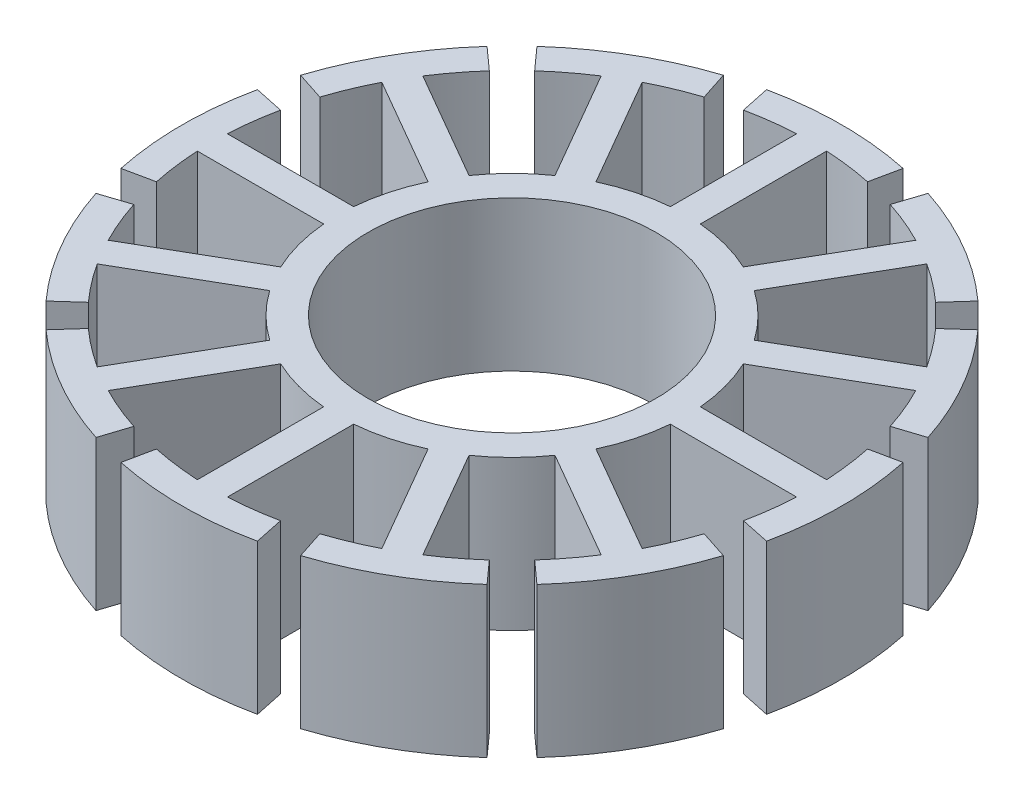
SolidWorks part; units mm, degrees
ref_plane "Front Plane" through (0, 0, 0) normal (0, 0, 1) x (1, 0, 0)
ref_plane "Top Plane" through (0, 0, 0) normal (0, 1, 0) x (1, 0, 0)
ref_plane "Right Plane" through (0, 0, 0) normal (1, 0, 0) x (0, 0, -1)
sketch "Sketch1" plane through (0, 0, 0) normal (0, 1, 0) x (1, 0, 0)
  line L0 (0, 11) -> (0, -11) construction
  line L1 (-0.5, 9.9875) -> (-0.5, 5.7784)
  line L2 (0.5, 9.9875) -> (0.5, 5.7784)
  line L3 (-2.0682, 9.7838) -> (-2.275, 10.7622)
  line L4 (2.0682, 9.7838) -> (2.275, 10.7622)
  line L5 (3.1008, 9.5071) -> (3.4109, 10.4578)
  line L6 (4.5607, 8.8994) -> (2.4562, 5.2542)
  line L7 (5.4268, 8.3994) -> (3.3222, 4.7542)
  line L8 (6.683, 7.4389) -> (7.3513, 8.1828)
  line L9 (7.4389, 6.683) -> (8.1828, 7.3513)
  line L10 (8.3994, 5.4268) -> (4.7542, 3.3222)
  line L11 (8.8994, 4.5607) -> (5.2542, 2.4562)
  line L12 (9.5071, 3.1008) -> (10.4578, 3.4109)
  line L13 (9.7838, 2.0682) -> (10.7622, 2.275)
  line L14 (9.9875, 0.5) -> (5.7784, 0.5)
  line L15 (9.9875, -0.5) -> (5.7784, -0.5)
  line L16 (9.7838, -2.0682) -> (10.7622, -2.275)
  line L17 (9.5071, -3.1008) -> (10.4578, -3.4109)
  line L18 (8.8994, -4.5607) -> (5.2542, -2.4562)
  line L19 (8.3994, -5.4268) -> (4.7542, -3.3222)
  line L20 (7.4389, -6.683) -> (8.1828, -7.3513)
  line L21 (6.683, -7.4389) -> (7.3513, -8.1828)
  line L22 (5.4268, -8.3994) -> (3.3222, -4.7542)
  line L23 (4.5607, -8.8994) -> (2.4562, -5.2542)
  line L24 (3.1008, -9.5071) -> (3.4109, -10.4578)
  line L25 (2.0682, -9.7838) -> (2.275, -10.7622)
  line L26 (0.5, -9.9875) -> (0.5, -5.7784)
  line L27 (-0.5, -9.9875) -> (-0.5, -5.7784)
  line L28 (-2.0682, -9.7838) -> (-2.275, -10.7622)
  line L29 (-3.1008, -9.5071) -> (-3.4109, -10.4578)
  line L30 (-4.5607, -8.8994) -> (-2.4562, -5.2542)
  line L31 (-5.4268, -8.3994) -> (-3.3222, -4.7542)
  line L32 (-6.683, -7.4389) -> (-7.3513, -8.1828)
  line L33 (-7.4389, -6.683) -> (-8.1828, -7.3513)
  line L34 (-8.3994, -5.4268) -> (-4.7542, -3.3222)
  line L35 (-8.8994, -4.5607) -> (-5.2542, -2.4562)
  line L36 (-9.5071, -3.1008) -> (-10.4578, -3.4109)
  line L37 (-9.7838, -2.0682) -> (-10.7622, -2.275)
  line L38 (-9.9875, -0.5) -> (-5.7784, -0.5)
  line L39 (-9.9875, 0.5) -> (-5.7784, 0.5)
  line L40 (-9.7838, 2.0682) -> (-10.7622, 2.275)
  line L41 (-9.5071, 3.1008) -> (-10.4578, 3.4109)
  line L42 (-8.8994, 4.5607) -> (-5.2542, 2.4562)
  line L43 (-8.3994, 5.4268) -> (-4.7542, 3.3222)
  line L44 (-7.4389, 6.683) -> (-8.1828, 7.3513)
  line L45 (-6.683, 7.4389) -> (-7.3513, 8.1828)
  line L46 (-5.4268, 8.3994) -> (-3.3222, 4.7542)
  line L47 (-4.5607, 8.8994) -> (-2.4562, 5.2542)
  line L48 (-3.1008, 9.5071) -> (-3.4109, 10.4578)
  circle A0 centre (0, 0) radius 4.8
  circle A1 centre (0, 0) radius 5.8
  circle A2 centre (0, 0) radius 11
  circle A3 centre (0, 0) radius 10
  point P106 (0, 0)
  dimension "D1" = 9.6
  dimension "D2" = 1
  dimension "D3" = 22
  dimension "D6" = 1
  dimension "D7" = 4.55
  dimension "D4" = 1
  dimension "D5" = 12
extrude "Boss-Extrude1" add sketch "Sketch1" along normal blind 5 contours A1 L0 A0 | L0 A1 A0 | L0 A3 L1 A1 | A3 L0 A1 L2 | A2 L0 A3 L4 | L0 A2 L3 A3 | L7 A3 L6 A1 | A3 L8 A2 L5 | L11 A3 L10 A1 | A3 L12 A2 L9 | L15 A3 L14 A1 | A3 L16 A2 L13 | L19 A3 L18 A1 | A3 L20 A2 L17 | L23 A3 L22 A1 | A3 L24 A2 L21 | L0 A1 L27 A3 | A1 L0 A3 L26 | A3 L0 A2 L25 | L0 A3 L28 A2 | L31 A3 L30 A1 | A3 L32 A2 L29 | L35 A3 L34 A1 | A3 L36 A2 L33 | L39 A3 L38 A1 | A3 L40 A2 L37 | L43 A3 L42 A1 | A3 L44 A2 L41 | L47 A3 L46 A1 | A3 L48 A2 L45 region at (1.0906, 0, -10.4321) region at (-1.0906, 0, -10.4321) region at (0.2501, 0, -7.8943) region at (-0.2501, 0, -7.8943) region at (0.2446, 0, -5.665) region at (-0.1297, 0, -5.3) region at (5.216, 0, -9.0345) region at (-5.216, 0, -9.0345) region at (3.9472, 0, -6.8367) region at (-3.9472, 0, -6.8367) region at (9.0345, 0, -5.216) region at (-9.0345, 0, -5.216) region at (0.2501, 0, 7.8943) region at (-0.2501, 0, 7.8943) region at (1.0906, 0, 10.4321) region at (-1.0906, 0, 10.4321) region at (6.8367, 0, -3.9472) region at (-6.8367, 0, -3.9472) region at (10.4321, 0, 0) region at (-10.4321, 0, 0) region at (-3.9472, 0, 6.8367) region at (3.9472, 0, 6.8367) region at (-5.216, 0, 9.0345) region at (5.216, 0, 9.0345) region at (7.8943, 0, 0) region at (-7.8943, 0, 0) region at (-9.0345, 0, 5.216) region at (-6.8367, 0, 3.9472) region at (6.8367, 0, 3.9472) region at (9.0345, 0, 5.216)
